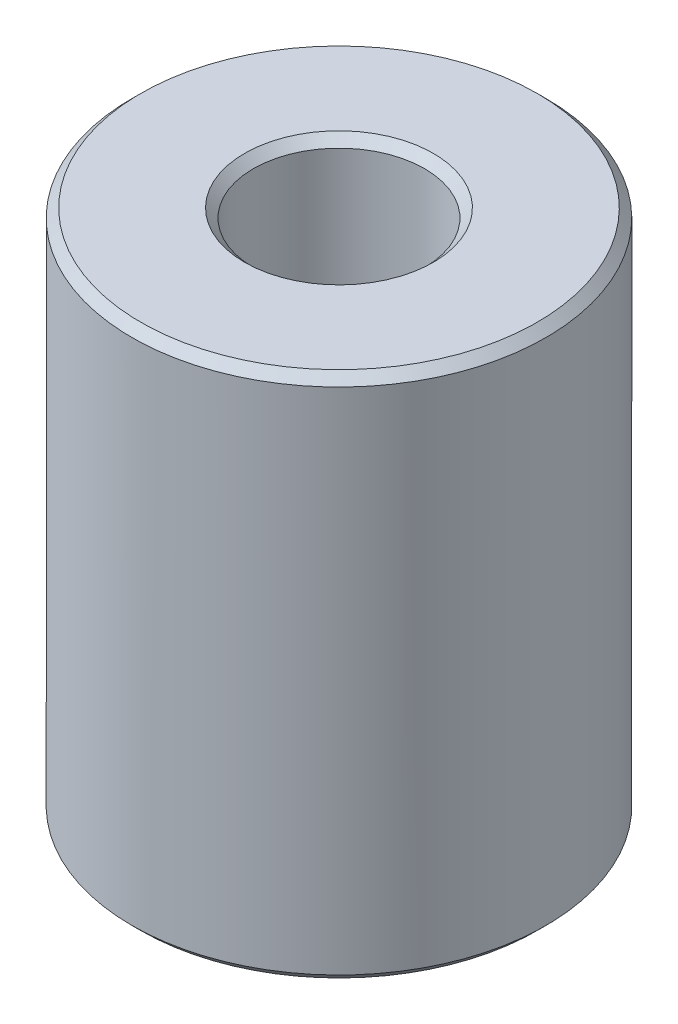
SolidWorks part; units mm, degrees
ref_plane "Front Plane" through (0, 0, 0) normal (0, 0, 1) x (1, 0, 0)
ref_plane "Top Plane" through (0, 0, 0) normal (0, 1, 0) x (1, 0, 0)
ref_plane "Right Plane" through (0, 0, 0) normal (1, 0, 0) x (0, 0, -1)
sketch "Sketch1" plane through (0, 0, 0) normal (0, 1, 0) x (1, 0, 0)
  circle A0 centre (0, 0) radius 60
  dimension "SLEEVE_OD" = 120
extrude "Boss-Extrude1" add sketch "Sketch1" along normal blind 152.6744
sketch "Sketch2" plane through (0, 0, 0) normal (0, 1, 0) x (1, 0, 0)
  circle A0 centre (0, 0) radius 24.7989
  dimension "BORE_D" = 49.5977
extrude "Cut-Extrude1" cut sketch "Sketch2" along normal through all
chamfer "Chamfer1" distance 2.5555 angle 45 4 edges at (0, 152.6744, 24.7989) (0, 0, 24.7989) (0, 0, 60) (0, 152.6744, 60)
